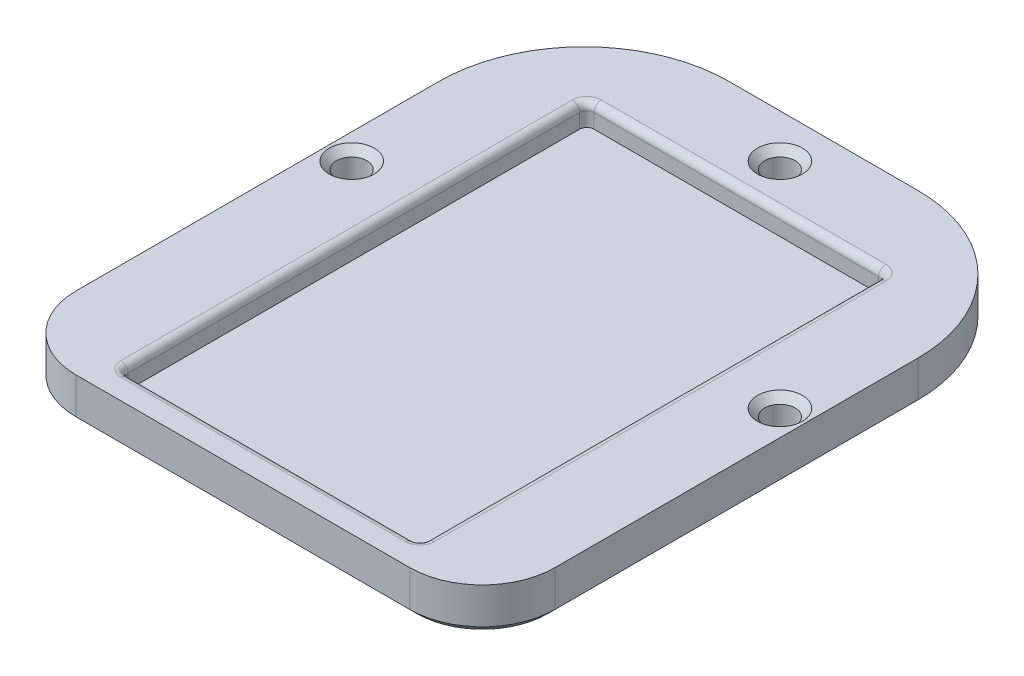
SolidWorks part; units mm, degrees
ref_plane "Спереди" through (0, 0, 0) normal (0, 0, 1) x (1, 0, 0)
ref_plane "Сверху" through (0, 0, 0) normal (0, 1, 0) x (1, 0, 0)
ref_plane "Справа" through (0, 0, 0) normal (1, 0, 0) x (0, 0, -1)
sketch "Эскиз1" plane through (0, 0, 0) normal (0, 1, 0) x (1, 0, 0)
  line L1 (-33, -40) -> (33, -40)
  line L2 (-33, -40) -> (-33, 40)
  line L3 (-33, 40) -> (33, 40)
  line L4 (33, -40) -> (33, 40)
  line L5 (0, 40) -> (0, -40) construction
  line L6 (-33, 0) -> (33, 0) construction
  point P0 (0, 0)
  dimension "D1" = 66
  dimension "D2" = 80
extrude "Бобышка-Вытянуть1" add sketch "Эскиз1" along normal blind 6
sketch "Эскиз2" plane through (0, 6, 0) normal (0, 1, 0) x (1, 0, 0)
  line L0 (0, 70.4628) -> (0, -72.8469) construction
  line L1 (33, 40) -> (-33, 40) construction
  line L2 (-20.6, -36.2) -> (20.6, -36.2)
  line L3 (-20.6, -36.2) -> (-20.6, 28)
  line L4 (-20.6, 28) -> (20.6, 28)
  line L5 (20.6, -36.2) -> (20.6, 28)
  line L6 (0, 28) -> (0, -36.2) construction
  line L7 (-20.6, -4.1) -> (20.6, -4.1) construction
  point P3 (0, -4.1)
  dimension "D1" = 41.2
  dimension "D2" = 64.2
  dimension "D3" = 12
extrude "Вырез-Вытянуть1" cut sketch "Эскиз2" against normal blind 3
fillet "Скругление1" radius 1 8 edges at (-20.6, 6, 4.1) (0, 6, 36.2) (0, 6, -28) (20.6, 6, 4.1) (20.6, 4.5, 36.2) (-20.6, 4.5, 36.2) (-20.6, 4.5, -28) (20.6, 4.5, -28)
sketch "Эскиз3" plane through (0, 6, 0) normal (0, 1, 0) x (1, 0, 0)
  line L0 (0, 41.5889) -> (0, -35) construction
  line L1 (-44.8515, 4.5) -> (85.6843, 4.5) construction
  line L2 (33, 40) -> (-33, 40) construction
  circle A15 centre (0, 34) radius 2.1
  circle A16 centre (-20.8597, 25.3597) radius 2.1
  circle A17 centre (-29.5, 4.5) radius 2.1
  circle A18 centre (-20.8597, -16.3597) radius 2.1
  circle A19 centre (0, -25) radius 2.1
  circle A20 centre (20.8597, -16.3597) radius 2.1
  circle A21 centre (29.5, 4.5) radius 2.1
  circle A22 centre (20.8597, 25.3597) radius 2.1
  point P25 (0, 4.5)
  dimension "D1" = 4.2
  dimension "D2" = 29.5
  dimension "D3" = 6
extrude "Вырез-Вытянуть2" cut sketch "Эскиз3" against normal through all contours A15 | A17 | A21
chamfer "Фаска1" distance 1 angle 45 3 edges at (0, 6, -31.9) (29.5, 6, -2.4) (-29.5, 6, -2.4)
fillet "Скругление2" radius 20 2 edges at (-33, 3, -40) (33, 3, -40)
fillet "Скругление3" radius 10 2 edges at (-33, 3, 40) (33, 3, 40)
chamfer "Фаска2" distance 1 angle 45 11 edges at (30.0711, 0, 37.0711) (33, 0, 5) (27.1421, 0, -34.1421) (0, 0, -40) (-27.1421, 0, -34.1421) (-33, 0, 5) (-30.0711, 0, 37.0711) (0, 0, 40) (29.5, 0, -2.4) (-29.5, 0, -2.4) (0, 0, -31.9)
